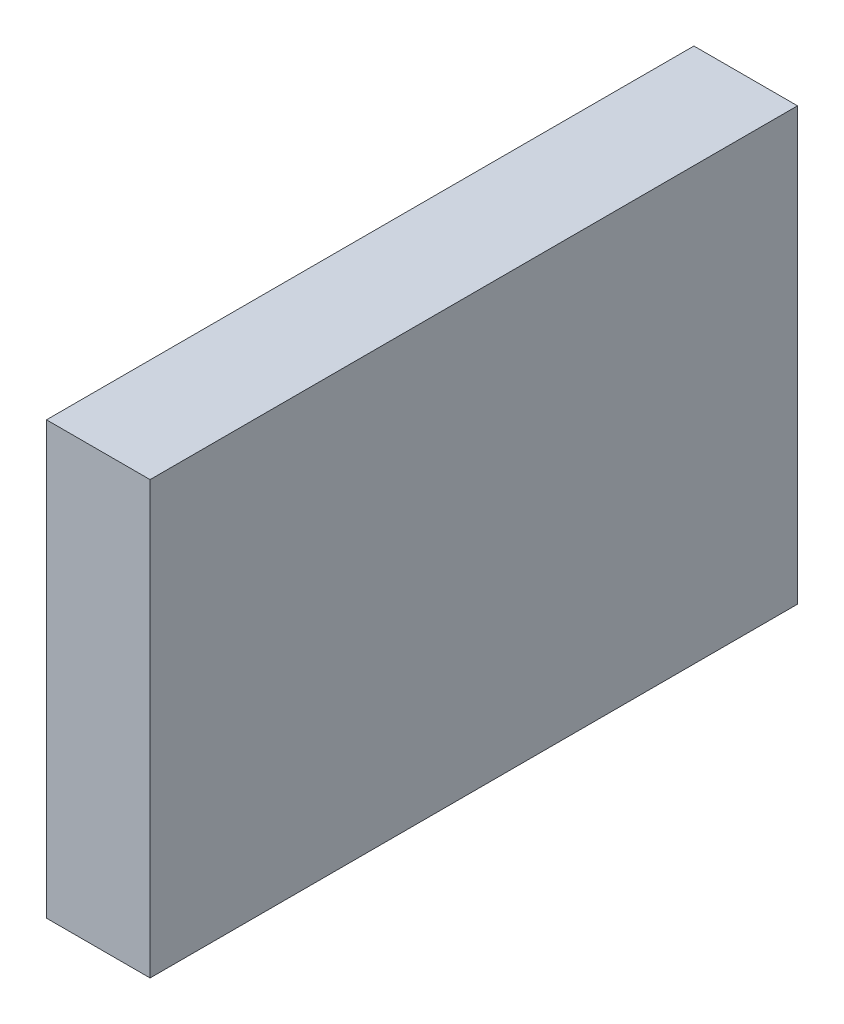
SolidWorks part; units mm, degrees
material "NEOPRENE"
ref_plane "Front" through (0, 0, 0) normal (0, 0, 1) x (1, 0, 0)
ref_plane "Top" through (0, 0, 0) normal (0, 1, 0) x (1, 0, 0)
ref_plane "Right" through (0, 0, 0) normal (1, 0, 0) x (0, 0, -1)
ref_axis "side-side" through (80.9, 0, 0) along (-1, 0, 0)
ref_axis "up-down" through (0, 50, 0) along (0, -1, 0)
ref_axis "front-back" through (0, 0, -80.9) along (0, 0, 1)
sketch "Sketch1" plane through (0, 0, 0) normal (1, 0, 0) x (0, 0, -1)
  line L0 (-38.1, 25.4) -> (38.1, -25.4) construction
  line L1 (-38.1, 25.4) -> (38.1, 25.4)
  line L2 (-38.1, 25.4) -> (-38.1, -25.4)
  line L3 (-38.1, -25.4) -> (38.1, -25.4)
  line L4 (38.1, 25.4) -> (38.1, -25.4)
  dimension "D1" = 76.2
  dimension "D2" = 50.8
extrude "Boss-Extrude1" add sketch "Sketch1" along normal blind 12.7
fillet "Fillet1" [suppressed] radius 10.16
chamfer "Chamfer1" distance 0.508 angle 45 4 edges at (0, -25.4, 0) (0, 0, -38.1) (0, 0, 38.1) (0, 25.4, 0)
